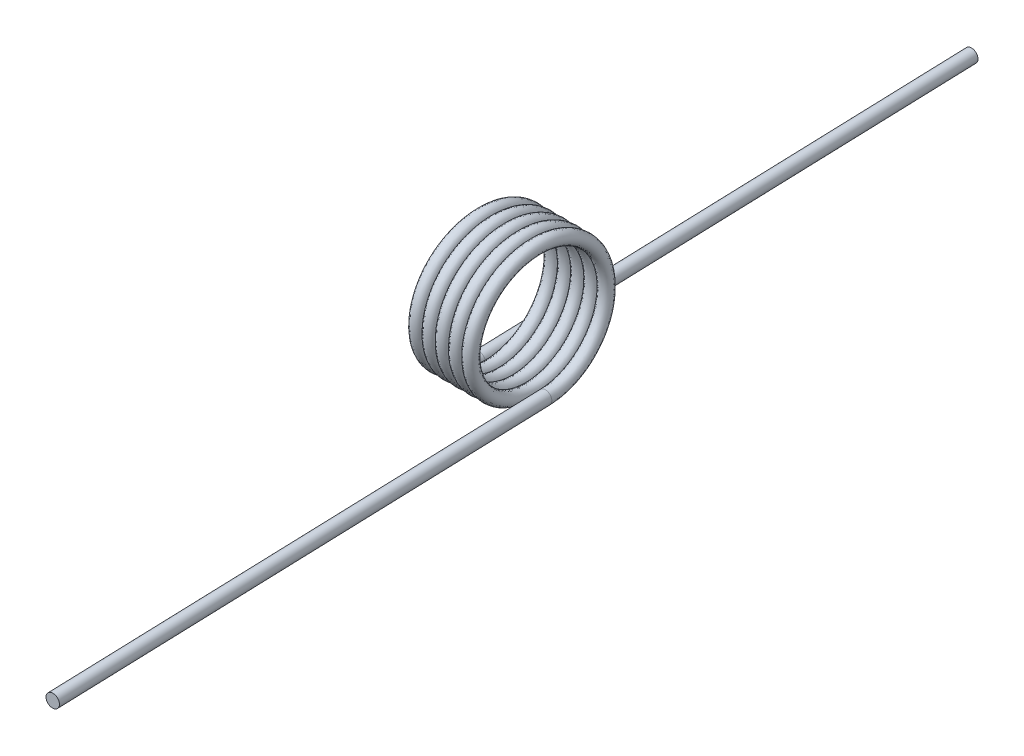
SolidWorks part; units mm, degrees
ref_plane "Front" through (0, 0, 0) normal (0, 0, 1) x (1, 0, 0)
ref_plane "Top" through (0, 0, 0) normal (0, 1, 0) x (1, 0, 0)
ref_plane "Right" through (0, 0, 0) normal (1, 0, 0) x (0, 0, -1)
sketch "Sketch1" plane through (0, 0, 0) normal (1, 0, 0) x (0, 0, -1)
  line L0 (0, -5.7658) -> (0, -7.0612) construction
  line L1 (0, -7.0612) -> (50.8, -7.0612) construction
  line L2 (0, -7.0612) -> (-50.8, -7.0612) construction
  line L3 (0, 0) -> (7.0612, 0) construction
  line L4 (0, 0) -> (0, -7.0612) construction
  line L5 (-50.8, -7.0612) -> (-50.8, -5.7658) construction
  line L6 (-50.8, -5.7658) -> (0, -5.7658) construction
  line L7 (50.8, -7.0612) -> (50.8, -5.7658) construction
  line L8 (50.8, -5.7658) -> (0, -5.7658) construction
  circle A0 centre (0, 0) radius 7.0612 construction
  circle A1 centre (0, 0) radius 4.7625 construction
  circle A2 centre (0, 0) radius 6.4135 construction
  point P7 (0, -6.4135)
  point P10 (0, 7.0612)
  dimension "OD" = 14.1224
  dimension "For Shaft Diameter" = 9.525
  dimension "Wire Diameter" = 1.2954
  dimension "Leg Length" = 50.8
  dimension "Deflection Angle" = 180
sketch "Sketch2" plane through (0, 0, 0) normal (1, 0, 0) x (0, 0, -1)
  circle A0 centre (0, 0) radius 6.4135 construction
  circle A2 centre (0, 0) radius 6.4135
curve "Helix/Spiral1" pitch 1.3208 height 6.604 turns 5
ref_plane "Plane1" through (0, -6.4135, 0) normal (-0.0328, 0, -0.9995) x (0.9992, -0.0232, -0.0328)
sketch "Sketch3" plane through (0, -6.4135, 0) normal (-0.0328, 0, -0.9995) x (0.9992, -0.0232, -0.0328)
  circle A0 centre (0, 0) radius 0.6477
  dimension "D1" = 1.2954
sweep "Sweep1" add profiles "Sketch3" path "Helix/Spiral1"
sketch "Sketch4" plane through (0, 0, 0) normal (0.0328, 0, 0.9995) x (-0.9992, 0.0232, 0.0328)
  circle A1 centre (-0.149, 6.4118) radius 0.6477
  circle A2 centre (-0.149, 6.4118) radius 0.6477
  dimension "D1" = 0
extrude "Extrude1" add sketch "Sketch4" along normal blind 50.8
sketch "Sketch5" plane through (-0.0071, 0, -0.2162) normal (-0.0328, 0, -0.9995) x (0.9985, 0.0449, -0.0327)
  circle A1 centre (-6.8816, 6.1109) radius 0.6477
  circle A2 centre (-6.8816, 6.1109) radius 0.6477
  dimension "D1" = 0
extrude "Extrude2" add sketch "Sketch5" along normal blind 50.8
sketch "Sketch6" plane through (0, 0, 0) normal (1, 0, 0) x (0, 0, -1)
  circle A2 centre (0, 0) radius 5.7658 construction
sketch "Sketch7" plane through (0, 0, 0) normal (1, 0, 0) x (0, 0, -1)
  circle A0 centre (0, 0) radius 5.6515
  dimension "D1" = 11.303
equation "\"D4@Helix/Spiral1\" = \"Wire Diameter@Sketch1\" + .001"
equation "\"D1@Sketch3\"=\"Wire Diameter@Sketch1\""
equation "\"D1@Extrude2\"=\"Leg Length@Sketch1\""
equation "\"Leg Length@Extrude1\"=\"Leg Length@Sketch1\""
